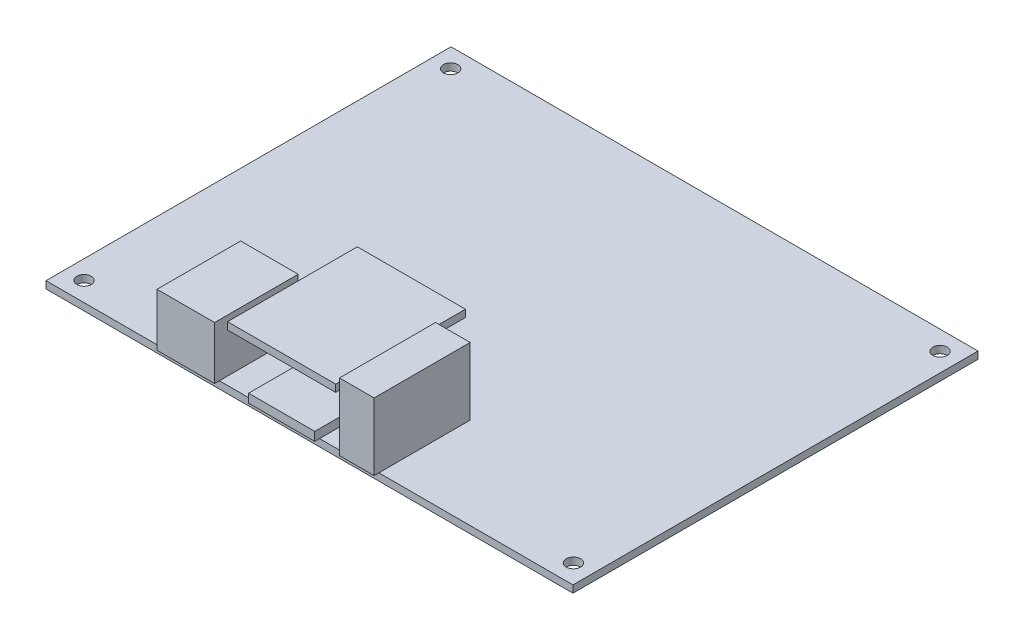
SolidWorks part; units mm, degrees
ref_plane "Front Plane" through (0, 0, 0) normal (0, 0, 1) x (1, 0, 0)
ref_plane "Top Plane" through (0, 0, 0) normal (0, 1, 0) x (1, 0, 0)
ref_plane "Right Plane" through (0, 0, 0) normal (1, 0, 0) x (0, 0, -1)
sketch "Sketch1" plane through (0, 0, 0) normal (0, 1, 0) x (1, 0, 0)
  line L1 (-50.925, -38.15) -> (50.925, -38.15) construction
  line L2 (-50.925, -38.15) -> (-50.925, 38.15) construction
  line L3 (-50.925, 38.15) -> (50.925, 38.15) construction
  line L4 (50.925, -38.15) -> (50.925, 38.15) construction
  line L5 (-50.925, -38.15) -> (50.925, 38.15) construction
  line L6 (-50.925, 38.15) -> (50.925, -38.15) construction
  line L7 (-54.835, -42.15) -> (54.835, -42.15)
  line L8 (-54.835, -42.15) -> (-54.835, 42.15)
  line L9 (-54.835, 42.15) -> (54.835, 42.15)
  line L10 (54.835, -42.15) -> (54.835, 42.15)
  line L11 (-54.835, -42.15) -> (54.835, 42.15) construction
  line L12 (-54.835, 42.15) -> (54.835, -42.15) construction
  line L13 (-30.725, -43.15) -> (-18.745, -43.15) construction
  line L14 (-30.725, -43.15) -> (-30.725, -25.75) construction
  line L15 (-30.725, -25.75) -> (-18.745, -25.75) construction
  line L16 (-18.745, -43.15) -> (-18.745, -25.75) construction
  line L17 (-16.045, -38.15) -> (6.455, -38.15) construction
  line L18 (-16.045, -38.15) -> (-16.045, -16.15) construction
  line L19 (-16.045, -16.15) -> (6.455, -16.15) construction
  line L20 (6.455, -38.15) -> (6.455, -16.15) construction
  line L21 (-11.665, -43.15) -> (2.095, -43.15) construction
  line L22 (-11.665, -43.15) -> (-11.665, -31.15) construction
  line L23 (-11.665, -31.15) -> (2.095, -31.15) construction
  line L24 (2.095, -43.15) -> (2.095, -31.15) construction
  line L25 (7.245, -43.15) -> (14.445, -43.15) construction
  line L26 (7.245, -43.15) -> (7.245, -23.15) construction
  line L27 (7.245, -23.15) -> (14.445, -23.15) construction
  line L28 (14.445, -43.15) -> (14.445, -23.15) construction
  circle A0 centre (-50.925, 38.15) radius 1.5
  circle A1 centre (-50.925, -38.15) radius 1.5
  circle A2 centre (50.925, -38.15) radius 1.5
  circle A3 centre (50.925, 38.15) radius 1.5
  point P0 (0, 0)
  point P6 (0, 0)
  point P31 (-11.665, -44.4558)
  dimension "D5" = 3
  dimension "D1" = 109.67
  dimension "D2" = 84.3
  dimension "D3" = 76.3
  dimension "D4" = 101.85
  dimension "D6" = 24.11
  dimension "D7" = 36.09
  dimension "D8" = 38.79
  dimension "D9" = 43.17
  dimension "D10" = 56.93
  dimension "D11" = 61.29
  dimension "D12" = 62.08
  dimension "D13" = 69.28
  dimension "D14" = 16.4
  dimension "D15" = 26
  dimension "D16" = 11
  dimension "D17" = 19
  dimension "D18" = 1
  dimension "D19" = 4
extrude "Boss-Extrude1" add sketch "Sketch1" against normal blind 1.5
sketch "Sketch2" plane through (0, 0, 0) normal (0, 1, 0) x (1, 0, 0)
  line L0 (-30.725, -25.75) -> (-18.745, -25.75) construction
  line L1 (-18.745, -43.15) -> (-18.745, -25.75) construction
  line L2 (-30.725, -43.15) -> (-18.745, -43.15) construction
  line L3 (-30.725, -43.15) -> (-30.725, -25.75) construction
  line L4 (-30.725, -25.75) -> (-18.745, -25.75)
  line L5 (-18.745, -43.15) -> (-18.745, -25.75)
  line L6 (-30.725, -43.15) -> (-18.745, -43.15)
  line L7 (-30.725, -43.15) -> (-30.725, -25.75)
extrude "Boss-Extrude2" add sketch "Sketch2" along normal blind 11 separate body
sketch "Sketch3" plane through (0, 0, 0) normal (0, 1, 0) x (1, 0, 0)
  line L0 (2.095, -43.15) -> (2.095, -31.15) construction
  line L1 (-11.665, -31.15) -> (2.095, -31.15) construction
  line L2 (-11.665, -43.15) -> (-11.665, -31.15) construction
  line L3 (2.095, -43.15) -> (2.095, -31.15)
  line L4 (-11.665, -31.15) -> (2.095, -31.15)
  line L5 (-11.665, -43.15) -> (-11.665, -31.15)
  line L6 (-11.665, -43.15) -> (2.095, -43.15)
extrude "Boss-Extrude3" add sketch "Sketch3" along normal blind 1.8 separate body
sketch "Sketch4" plane through (0, 0, 0) normal (0, 1, 0) x (1, 0, 0)
  line L0 (14.445, -43.15) -> (14.445, -23.15) construction
  line L1 (7.245, -23.15) -> (14.445, -23.15) construction
  line L2 (7.245, -43.15) -> (7.245, -23.15) construction
  line L3 (7.245, -43.15) -> (14.445, -43.15) construction
  line L4 (14.445, -43.15) -> (14.445, -23.15)
  line L5 (7.245, -23.15) -> (14.445, -23.15)
  line L6 (7.245, -43.15) -> (7.245, -23.15)
  line L7 (7.245, -43.15) -> (14.445, -43.15)
extrude "Boss-Extrude4" add sketch "Sketch4" along normal blind 14 separate body
ref_plane "Plane1" through (0, 11, 0) normal (0, 1, 0) x (1, 0, 0)
sketch "Sketch5" plane through (0, 11, 0) normal (0, 1, 0) x (1, 0, 0)
  line L0 (6.455, -43.15) -> (6.455, -16.15) construction
  line L1 (-16.045, -16.15) -> (6.455, -16.15) construction
  line L2 (-16.045, -43.15) -> (6.455, -43.15) construction
  line L3 (-16.045, -43.15) -> (-16.045, -16.15) construction
  line L4 (6.455, -43.15) -> (6.455, -16.15)
  line L5 (-16.045, -16.15) -> (6.455, -16.15)
  line L6 (-16.045, -43.15) -> (6.455, -43.15)
  line L7 (-16.045, -43.15) -> (-16.045, -16.15)
extrude "Boss-Extrude5" add sketch "Sketch5" along normal blind 1.5 separate body
